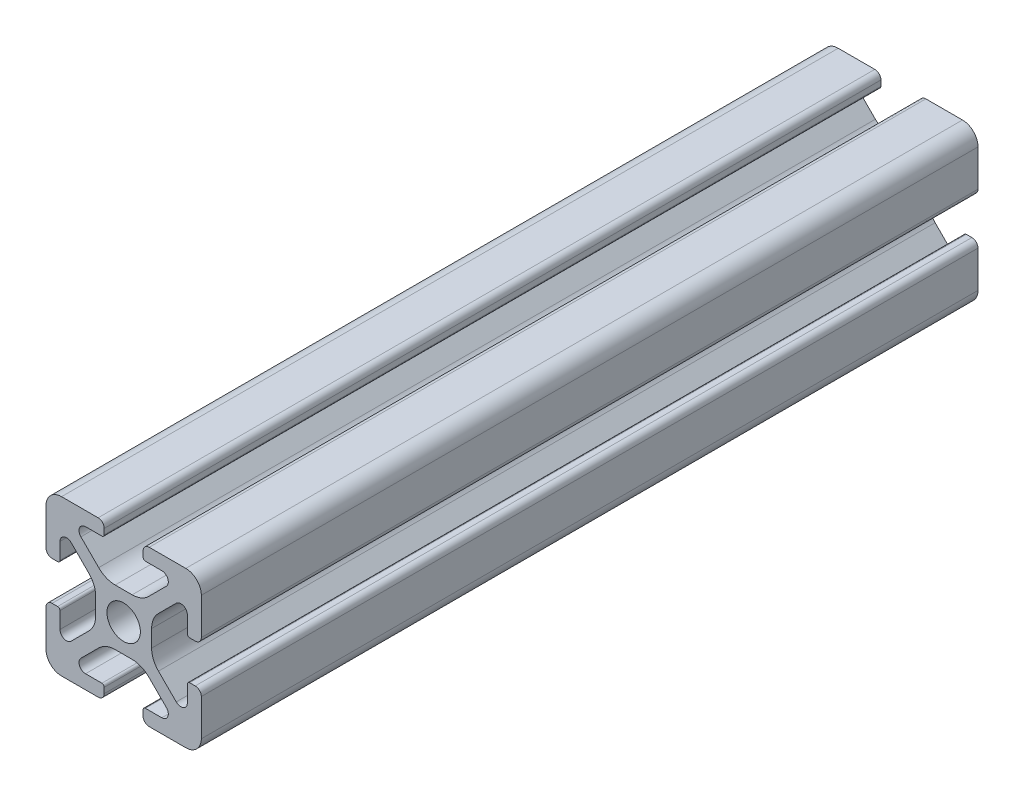
SolidWorks part; units mm, degrees
ref_plane "Front Plane" through (0, 0, 0) normal (0, 0, 1) x (1, 0, 0)
ref_plane "Top Plane" through (0, 0, 0) normal (0, 1, 0) x (1, 0, 0)
ref_plane "Right Plane" through (0, 0, 0) normal (1, 0, 0) x (0, 0, -1)
sketch "Sketch1" plane through (0, 0, 0) normal (0, 0, 1) x (1, 0, 0)
  line L0 (0, 10) -> (0, -10) construction
  line L1 (10, 0) -> (-10, 0) construction
  line L2 (-2.5, 10) -> (2.5, 10) construction
  line L3 (-5.75, 8.2) -> (5.75, 8.2) construction
  circle A0 centre (0, 0) radius 2.15 construction
  point P4 (0, 0)
  point P8 (0, 0)
  point P10 (0, 3.6)
  point P14 (0, 10)
  point P17 (0, 8.2)
  dimension "Thru Hole" = 4.3
  dimension "Height" = 20
  dimension "T Slot Depth" = 6.4
  dimension "T Slot Top Width" = 5
  dimension "T Slot Max Width" = 11.5
  dimension "Wall" = 1.8
sketch "Sketch2" plane through (0, 0, 0) normal (1, 0, 0) x (0, 0, -1)
  line L0 (152.4, 0) -> (-152.4, 0) construction
  point P4 (0, 0)
  dimension "D1" = 304.8
sketch "Sketch3" plane through (0, 0, 0) normal (0, 0, 1) x (1, 0, 0)
  line L0 (3.2874, 10) -> (8, 10)
  line L1 (10, 8) -> (10, -8) construction
  line L2 (8, -10) -> (-8, -10) construction
  line L3 (-10, 10) -> (10, -10) construction
  line L4 (2.5, 9.2126) -> (2.5, 8.5048)
  line L5 (-5.75, 8.2) -> (5.75, 8.2) construction
  line L6 (2.8048, 8.2) -> (4.9118, 8.2)
  line L7 (5.5045, 6.7691) -> (3.2141, 4.4787)
  line L8 (1.0928, 3.6) -> (-1.0928, 3.6)
  line L9 (0, 10) -> (0, -10) construction
  line L10 (5.75, 8.2) -> (5.75, 0) construction
  line L11 (10, 0) -> (-10, 0) construction
  line L12 (0, 0) -> (0, 10) construction
  line L13 (-2.5, 9.2126) -> (-2.5, 8.5048)
  line L14 (-5.5045, 6.7691) -> (-3.2141, 4.4787)
  line L15 (-2.8048, 8.2) -> (-4.9118, 8.2)
  line L16 (-3.2874, 10) -> (-8, 10)
  line L17 (0, 0) -> (-10, 0) construction
  line L18 (-10, 3.2874) -> (-10, 8)
  line L19 (-8.2, 2.8048) -> (-8.2, 4.9118)
  line L20 (-6.7691, 5.5045) -> (-4.4787, 3.2141)
  line L21 (-9.2126, 2.5) -> (-8.5048, 2.5)
  line L22 (-3.6, -1.0928) -> (-3.6, 1.0928)
  line L23 (-6.7691, -5.5045) -> (-4.4787, -3.2141)
  line L24 (-8.2, -2.8048) -> (-8.2, -4.9118)
  line L25 (-9.2126, -2.5) -> (-8.5048, -2.5)
  line L26 (-10, -3.2874) -> (-10, -8)
  line L27 (9.2126, -2.5) -> (8.5048, -2.5)
  line L28 (8.2, -2.8048) -> (8.2, -4.9118)
  line L29 (6.7691, -5.5045) -> (4.4787, -3.2141)
  line L30 (3.6, -1.0928) -> (3.6, 1.0928)
  line L31 (9.2126, 2.5) -> (8.5048, 2.5)
  line L32 (6.7691, 5.5045) -> (4.4787, 3.2141)
  line L33 (8.2, 2.8048) -> (8.2, 4.9118)
  line L34 (10, 8) -> (10, 3.2874)
  line L35 (10, -3.2874) -> (10, -8)
  line L36 (3.2874, -10) -> (8, -10)
  line L37 (-3.2874, -10) -> (-8, -10)
  line L38 (-6.7691, -5.5045) -> (-4.4787, -3.2141)
  line L39 (-2.8048, -8.2) -> (-4.9118, -8.2)
  line L40 (-5.5045, -6.7691) -> (-3.2141, -4.4787)
  line L41 (-2.5, -9.2126) -> (-2.5, -8.5048)
  line L42 (1.0928, -3.6) -> (-1.0928, -3.6)
  line L43 (5.5045, -6.7691) -> (3.2141, -4.4787)
  line L44 (2.8048, -8.2) -> (4.9118, -8.2)
  line L45 (2.5, -9.2126) -> (2.5, -8.5048)
  arc A0 (4.9118, 8.2) -> (5.5045, 6.7691) centre (4.9118, 7.3618) cw
  arc A1 (3.2141, 4.4787) -> (1.0928, 3.6) centre (1.0928, 6.6) cw
  circle A2 centre (0, 0) radius 2.15 construction
  circle A3 centre (0, 0) radius 2.15
  arc A4 (3.2874, 10) -> (2.5, 9.2126) centre (3.2874, 9.2126) ccw
  arc A5 (2.5, 8.5048) -> (2.8048, 8.2) centre (2.8048, 8.5048) ccw
  arc A6 (-3.2874, 10) -> (-2.5, 9.2126) centre (-3.2874, 9.2126) cw
  arc A7 (-4.9118, 8.2) -> (-5.5045, 6.7691) centre (-4.9118, 7.3618) ccw
  arc A8 (-3.2141, 4.4787) -> (-1.0928, 3.6) centre (-1.0928, 6.6) ccw
  arc A9 (-2.5, 8.5048) -> (-2.8048, 8.2) centre (-2.8048, 8.5048) cw
  arc A10 (-8.5048, 2.5) -> (-8.2, 2.8048) centre (-8.5048, 2.8048) ccw
  arc A11 (-4.4787, 3.2141) -> (-3.6, 1.0928) centre (-6.6, 1.0928) cw
  arc A12 (-8.2, 4.9118) -> (-6.7691, 5.5045) centre (-7.3618, 4.9118) cw
  arc A13 (-10, 3.2874) -> (-9.2126, 2.5) centre (-9.2126, 3.2874) ccw
  arc A14 (-8.5048, -2.5) -> (-8.2, -2.8048) centre (-8.5048, -2.8048) cw
  arc A15 (-10, -3.2874) -> (-9.2126, -2.5) centre (-9.2126, -3.2874) cw
  arc A16 (-4.4787, -3.2141) -> (-3.6, -1.0928) centre (-6.6, -1.0928) ccw
  arc A17 (-8.2, -4.9118) -> (-6.7691, -5.5045) centre (-7.3618, -4.9118) ccw
  arc A26 (-8, -10) -> (-10, -8) centre (-8, -8) cw
  arc A27 (-8, 10) -> (-10, 8) centre (-8, 8) ccw
  arc A28 (8, 10) -> (10, 8) centre (8, 8) cw
  arc A29 (10, -8) -> (8, -10) centre (8, -8) cw
  arc A30 (8.2, -4.9118) -> (6.7691, -5.5045) centre (7.3618, -4.9118) cw
  arc A31 (4.4787, -3.2141) -> (3.6, -1.0928) centre (6.6, -1.0928) cw
  arc A32 (10, -3.2874) -> (9.2126, -2.5) centre (9.2126, -3.2874) ccw
  arc A33 (8.5048, -2.5) -> (8.2, -2.8048) centre (8.5048, -2.8048) ccw
  arc A34 (10, 3.2874) -> (9.2126, 2.5) centre (9.2126, 3.2874) cw
  arc A35 (8.2, 4.9118) -> (6.7691, 5.5045) centre (7.3618, 4.9118) ccw
  arc A36 (4.4787, 3.2141) -> (3.6, 1.0928) centre (6.6, 1.0928) ccw
  arc A37 (8.5048, 2.5) -> (8.2, 2.8048) centre (8.5048, 2.8048) cw
  arc A38 (-2.5, -8.5048) -> (-2.8048, -8.2) centre (-2.8048, -8.5048) ccw
  arc A39 (-3.2141, -4.4787) -> (-1.0928, -3.6) centre (-1.0928, -6.6) cw
  arc A40 (-4.9118, -8.2) -> (-5.5045, -6.7691) centre (-4.9118, -7.3618) cw
  arc A41 (-3.2874, -10) -> (-2.5, -9.2126) centre (-3.2874, -9.2126) ccw
  arc A42 (2.5, -8.5048) -> (2.8048, -8.2) centre (2.8048, -8.5048) cw
  arc A43 (3.2874, -10) -> (2.5, -9.2126) centre (3.2874, -9.2126) cw
  arc A44 (3.2141, -4.4787) -> (1.0928, -3.6) centre (1.0928, -6.6) ccw
  arc A45 (4.9118, -8.2) -> (5.5045, -6.7691) centre (4.9118, -7.3618) ccw
  point P36 (2.5, 10)
  point P39 (2.5, 8.2)
  point P49 (0, 3.6)
  point P77 (-3.6, 0)
  point P78 (-8.2, -2.5)
  point P79 (-10, -2.5)
  point P104 (-10, -10)
  point P110 (10, 10)
  point P114 (10, -2.5)
  point P115 (8.2, -2.5)
  point P116 (3.6, 0)
  point P141 (0, -3.6)
  dimension "D1" = 3
  dimension "D2" = 0.8382
  dimension "D4" = 0.7874
  dimension "D5" = 0.3048
  dimension "D6" = 2
  dimension "D3" = 45
extrude "Boss-Extrude1" add sketch "Sketch3" along normal blind 50 and the other way blind 50 contours A45 L44 A42 L45 A43 L36 A29 L35 A32 L27 A33 L28 A30 L29 A31 L30 A36 L32 A35 L33 A37 L31 A34 L34 A28 L0 A4 L4 A5 L6 A0 L7 A1 L8 A8 L14 A7 L15 A9 L13 A6 L16 A27 L18 A13 L21 A10 L19 A12 L20 A11 region at (5.6437, 9.7172, 0)
sketch "Sketch4" plane through (0, 0, -50) normal (0, 0, -1) x (-1, 0, 0)
  line L0 (9.4142, 9.4142) -> (-9.4142, -9.4142) construction
  line L1 (-9.4142, 9.4142) -> (9.4142, -9.4142) construction
  arc A0 (10, 8) -> (8, 10) centre (8, 8) ccw construction
  arc A1 (-10, -8) -> (-8, -10) centre (-8, -8) ccw construction
  arc A2 (-8, 10) -> (-10, 8) centre (-8, 8) ccw construction
  arc A3 (8, -10) -> (10, -8) centre (8, -8) ccw construction
sketch "Sketch5" plane through (0, 0, 50) normal (0, 0, 1) x (1, 0, 0)
  line L0 (9.4142, 9.4142) -> (-9.4142, -9.4142) construction
  line L1 (-9.4142, 9.4142) -> (9.4142, -9.4142) construction
  arc A0 (10, 8) -> (8, 10) centre (8, 8) ccw construction
sketch "Sketch6" plane through (0, 0, 50) normal (0, 0, 1) x (1, 0, 0)
  line L36 (4.9118, -8.2) -> (2.8048, -8.2)
  line L37 (2.5, -8.5048) -> (2.5, -9.2126)
  line L38 (3.2874, -10) -> (8, -10)
  line L39 (10, -8) -> (10, -3.2874)
  line L40 (9.2126, -2.5) -> (8.5048, -2.5)
  line L41 (8.2, -2.8048) -> (8.2, -4.9118)
  line L42 (6.7691, -5.5045) -> (4.4787, -3.2141)
  line L43 (3.6, -1.0928) -> (3.6, 1.0928)
  line L44 (4.4787, 3.2141) -> (6.7691, 5.5045)
  line L45 (8.2, 4.9118) -> (8.2, 2.8048)
  line L46 (8.5048, 2.5) -> (9.2126, 2.5)
  line L47 (10, 3.2874) -> (10, 8)
  line L48 (8, 10) -> (3.2874, 10)
  line L49 (2.5, 9.2126) -> (2.5, 8.5048)
  line L50 (2.8048, 8.2) -> (4.9118, 8.2)
  line L51 (5.5045, 6.7691) -> (3.2141, 4.4787)
  line L52 (1.0928, 3.6) -> (-1.0928, 3.6)
  line L53 (-3.2141, 4.4787) -> (-5.5045, 6.7691)
  line L54 (-4.9118, 8.2) -> (-2.8048, 8.2)
  line L55 (-2.5, 8.5048) -> (-2.5, 9.2126)
  line L56 (-3.2874, 10) -> (-8, 10)
  line L57 (-10, 8) -> (-10, 3.2874)
  line L58 (-9.2126, 2.5) -> (-8.5048, 2.5)
  line L59 (-8.2, 2.8048) -> (-8.2, 4.9118)
  line L60 (-6.7691, 5.5045) -> (-4.4787, 3.2141)
  line L61 (-3.6, 1.0928) -> (-3.6, -1.0928)
  line L62 (-4.4787, -3.2141) -> (-6.7691, -5.5045)
  line L63 (-8.2, -4.9118) -> (-8.2, -2.8048)
  line L64 (-8.5048, -2.5) -> (-9.2126, -2.5)
  line L65 (-10, -3.2874) -> (-10, -8)
  line L66 (-8, -10) -> (-3.2874, -10)
  line L67 (-2.5, -9.2126) -> (-2.5, -8.5048)
  line L68 (-2.8048, -8.2) -> (-4.9118, -8.2)
  line L69 (-5.5045, -6.7691) -> (-3.2141, -4.4787)
  line L70 (-1.0928, -3.6) -> (1.0928, -3.6)
  line L71 (3.2141, -4.4787) -> (5.5045, -6.7691)
  line L72 (4.9118, -8.2) -> (2.8048, -8.2)
  line L73 (2.5, -8.5048) -> (2.5, -9.2126)
  line L74 (3.2874, -10) -> (8, -10)
  line L75 (10, -8) -> (10, -3.2874)
  line L76 (9.2126, -2.5) -> (8.5048, -2.5)
  line L77 (8.2, -2.8048) -> (8.2, -4.9118)
  line L78 (6.7691, -5.5045) -> (4.4787, -3.2141)
  line L79 (3.6, -1.0928) -> (3.6, 1.0928)
  line L80 (4.4787, 3.2141) -> (6.7691, 5.5045)
  line L81 (8.2, 4.9118) -> (8.2, 2.8048)
  line L82 (8.5048, 2.5) -> (9.2126, 2.5)
  line L83 (10, 3.2874) -> (10, 8)
  line L84 (8, 10) -> (3.2874, 10)
  line L85 (2.5, 9.2126) -> (2.5, 8.5048)
  line L86 (2.8048, 8.2) -> (4.9118, 8.2)
  line L87 (5.5045, 6.7691) -> (3.2141, 4.4787)
  line L88 (1.0928, 3.6) -> (-1.0928, 3.6)
  line L89 (-3.2141, 4.4787) -> (-5.5045, 6.7691)
  line L90 (-4.9118, 8.2) -> (-2.8048, 8.2)
  line L91 (-2.5, 8.5048) -> (-2.5, 9.2126)
  line L92 (-3.2874, 10) -> (-8, 10)
  line L93 (-10, 8) -> (-10, 3.2874)
  line L94 (-9.2126, 2.5) -> (-8.5048, 2.5)
  line L95 (-8.2, 2.8048) -> (-8.2, 4.9118)
  line L96 (-6.7691, 5.5045) -> (-4.4787, 3.2141)
  line L97 (-3.6, 1.0928) -> (-3.6, -1.0928)
  line L98 (-4.4787, -3.2141) -> (-6.7691, -5.5045)
  line L99 (-8.2, -4.9118) -> (-8.2, -2.8048)
  line L100 (-8.5048, -2.5) -> (-9.2126, -2.5)
  line L101 (-10, -3.2874) -> (-10, -8)
  line L102 (-8, -10) -> (-3.2874, -10)
  line L103 (-2.5, -9.2126) -> (-2.5, -8.5048)
  line L104 (-2.8048, -8.2) -> (-4.9118, -8.2)
  line L105 (-5.5045, -6.7691) -> (-3.2141, -4.4787)
  line L106 (-1.0928, -3.6) -> (1.0928, -3.6)
  line L107 (3.2141, -4.4787) -> (5.5045, -6.7691)
  circle A1 centre (0, 0) radius 2.15
  circle A2 centre (0, 0) radius 2.15
  arc A38 (4.9118, -8.2) -> (5.5045, -6.7691) centre (4.9118, -7.3618) ccw
  arc A39 (2.8048, -8.2) -> (2.5, -8.5048) centre (2.8048, -8.5048) ccw
  arc A40 (2.5, -9.2126) -> (3.2874, -10) centre (3.2874, -9.2126) ccw
  arc A41 (8, -10) -> (10, -8) centre (8, -8) ccw
  arc A42 (10, -3.2874) -> (9.2126, -2.5) centre (9.2126, -3.2874) ccw
  arc A43 (8.5048, -2.5) -> (8.2, -2.8048) centre (8.5048, -2.8048) ccw
  arc A44 (6.7691, -5.5045) -> (8.2, -4.9118) centre (7.3618, -4.9118) ccw
  arc A45 (3.6, -1.0928) -> (4.4787, -3.2141) centre (6.6, -1.0928) ccw
  arc A46 (4.4787, 3.2141) -> (3.6, 1.0928) centre (6.6, 1.0928) ccw
  arc A47 (8.2, 4.9118) -> (6.7691, 5.5045) centre (7.3618, 4.9118) ccw
  arc A48 (8.2, 2.8048) -> (8.5048, 2.5) centre (8.5048, 2.8048) ccw
  arc A49 (9.2126, 2.5) -> (10, 3.2874) centre (9.2126, 3.2874) ccw
  arc A50 (10, 8) -> (8, 10) centre (8, 8) ccw
  arc A51 (3.2874, 10) -> (2.5, 9.2126) centre (3.2874, 9.2126) ccw
  arc A52 (2.5, 8.5048) -> (2.8048, 8.2) centre (2.8048, 8.5048) ccw
  arc A53 (5.5045, 6.7691) -> (4.9118, 8.2) centre (4.9118, 7.3618) ccw
  arc A54 (1.0928, 3.6) -> (3.2141, 4.4787) centre (1.0928, 6.6) ccw
  arc A55 (-3.2141, 4.4787) -> (-1.0928, 3.6) centre (-1.0928, 6.6) ccw
  arc A56 (-4.9118, 8.2) -> (-5.5045, 6.7691) centre (-4.9118, 7.3618) ccw
  arc A57 (-2.8048, 8.2) -> (-2.5, 8.5048) centre (-2.8048, 8.5048) ccw
  arc A58 (-2.5, 9.2126) -> (-3.2874, 10) centre (-3.2874, 9.2126) ccw
  arc A59 (-8, 10) -> (-10, 8) centre (-8, 8) ccw
  arc A60 (-10, 3.2874) -> (-9.2126, 2.5) centre (-9.2126, 3.2874) ccw
  arc A61 (-8.5048, 2.5) -> (-8.2, 2.8048) centre (-8.5048, 2.8048) ccw
  arc A62 (-6.7691, 5.5045) -> (-8.2, 4.9118) centre (-7.3618, 4.9118) ccw
  arc A63 (-3.6, 1.0928) -> (-4.4787, 3.2141) centre (-6.6, 1.0928) ccw
  arc A64 (-4.4787, -3.2141) -> (-3.6, -1.0928) centre (-6.6, -1.0928) ccw
  arc A65 (-8.2, -4.9118) -> (-6.7691, -5.5045) centre (-7.3618, -4.9118) ccw
  arc A66 (-8.2, -2.8048) -> (-8.5048, -2.5) centre (-8.5048, -2.8048) ccw
  arc A67 (-9.2126, -2.5) -> (-10, -3.2874) centre (-9.2126, -3.2874) ccw
  arc A68 (-10, -8) -> (-8, -10) centre (-8, -8) ccw
  arc A69 (-3.2874, -10) -> (-2.5, -9.2126) centre (-3.2874, -9.2126) ccw
  arc A70 (-2.5, -8.5048) -> (-2.8048, -8.2) centre (-2.8048, -8.5048) ccw
  arc A71 (-5.5045, -6.7691) -> (-4.9118, -8.2) centre (-4.9118, -7.3618) ccw
  arc A72 (-1.0928, -3.6) -> (-3.2141, -4.4787) centre (-1.0928, -6.6) ccw
  arc A73 (3.2141, -4.4787) -> (1.0928, -3.6) centre (1.0928, -6.6) ccw
  arc A74 (4.9118, -8.2) -> (5.5045, -6.7691) centre (4.9118, -7.3618) ccw
  arc A75 (2.8048, -8.2) -> (2.5, -8.5048) centre (2.8048, -8.5048) ccw
  arc A76 (2.5, -9.2126) -> (3.2874, -10) centre (3.2874, -9.2126) ccw
  arc A77 (8, -10) -> (10, -8) centre (8, -8) ccw
  arc A78 (10, -3.2874) -> (9.2126, -2.5) centre (9.2126, -3.2874) ccw
  arc A79 (8.5048, -2.5) -> (8.2, -2.8048) centre (8.5048, -2.8048) ccw
  arc A80 (6.7691, -5.5045) -> (8.2, -4.9118) centre (7.3618, -4.9118) ccw
  arc A81 (3.6, -1.0928) -> (4.4787, -3.2141) centre (6.6, -1.0928) ccw
  arc A82 (4.4787, 3.2141) -> (3.6, 1.0928) centre (6.6, 1.0928) ccw
  arc A83 (8.2, 4.9118) -> (6.7691, 5.5045) centre (7.3618, 4.9118) ccw
  arc A84 (8.2, 2.8048) -> (8.5048, 2.5) centre (8.5048, 2.8048) ccw
  arc A85 (9.2126, 2.5) -> (10, 3.2874) centre (9.2126, 3.2874) ccw
  arc A86 (10, 8) -> (8, 10) centre (8, 8) ccw
  arc A87 (3.2874, 10) -> (2.5, 9.2126) centre (3.2874, 9.2126) ccw
  arc A88 (2.5, 8.5048) -> (2.8048, 8.2) centre (2.8048, 8.5048) ccw
  arc A89 (5.5045, 6.7691) -> (4.9118, 8.2) centre (4.9118, 7.3618) ccw
  arc A90 (1.0928, 3.6) -> (3.2141, 4.4787) centre (1.0928, 6.6) ccw
  arc A91 (-3.2141, 4.4787) -> (-1.0928, 3.6) centre (-1.0928, 6.6) ccw
  arc A92 (-4.9118, 8.2) -> (-5.5045, 6.7691) centre (-4.9118, 7.3618) ccw
  arc A93 (-2.8048, 8.2) -> (-2.5, 8.5048) centre (-2.8048, 8.5048) ccw
  arc A94 (-2.5, 9.2126) -> (-3.2874, 10) centre (-3.2874, 9.2126) ccw
  arc A95 (-8, 10) -> (-10, 8) centre (-8, 8) ccw
  arc A96 (-10, 3.2874) -> (-9.2126, 2.5) centre (-9.2126, 3.2874) ccw
  arc A97 (-8.5048, 2.5) -> (-8.2, 2.8048) centre (-8.5048, 2.8048) ccw
  arc A98 (-6.7691, 5.5045) -> (-8.2, 4.9118) centre (-7.3618, 4.9118) ccw
  arc A99 (-3.6, 1.0928) -> (-4.4787, 3.2141) centre (-6.6, 1.0928) ccw
  arc A100 (-4.4787, -3.2141) -> (-3.6, -1.0928) centre (-6.6, -1.0928) ccw
  arc A101 (-8.2, -4.9118) -> (-6.7691, -5.5045) centre (-7.3618, -4.9118) ccw
  arc A102 (-8.2, -2.8048) -> (-8.5048, -2.5) centre (-8.5048, -2.8048) ccw
  arc A103 (-9.2126, -2.5) -> (-10, -3.2874) centre (-9.2126, -3.2874) ccw
  arc A104 (-10, -8) -> (-8, -10) centre (-8, -8) ccw
  arc A105 (-3.2874, -10) -> (-2.5, -9.2126) centre (-3.2874, -9.2126) ccw
  arc A106 (-2.5, -8.5048) -> (-2.8048, -8.2) centre (-2.8048, -8.5048) ccw
  arc A107 (-5.5045, -6.7691) -> (-4.9118, -8.2) centre (-4.9118, -7.3618) ccw
  arc A108 (-1.0928, -3.6) -> (-3.2141, -4.4787) centre (-1.0928, -6.6) ccw
  arc A109 (3.2141, -4.4787) -> (1.0928, -3.6) centre (1.0928, -6.6) ccw
  dimension "D1" = 0
  dimension "D2" = 0
